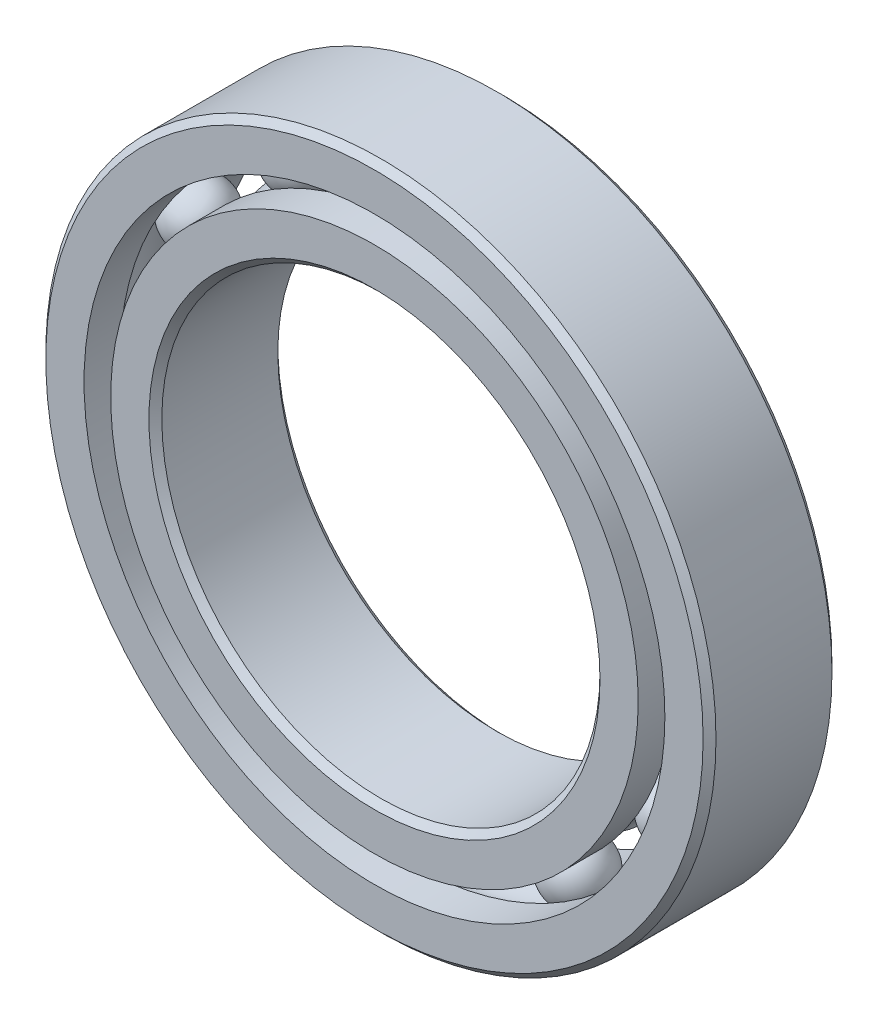
SolidWorks part; units mm, degrees
ref_plane "Front Plane" through (0, 0, 0) normal (0, 0, 1) x (1, 0, 0)
ref_plane "Top Plane" through (0, 0, 0) normal (0, 1, 0) x (1, 0, 0)
ref_plane "Right Plane" through (0, 0, 0) normal (1, 0, 0) x (0, 0, -1)
sketch "Sketch1" plane through (0, 0, 0) normal (1, 0, 0) x (0, 0, -1)
  line L0 (-2.5, 0) -> (2.5, 0) construction
  line L1 (0, 13) -> (0, -13) construction
  line L2 (2.25, 13) -> (-2.25, 13)
  line L3 (-2.25, 13) -> (-2.5, 12.75)
  line L4 (-2.5, 12.75) -> (-2.5, 11.2674)
  line L5 (-2.5, 11.2674) -> (-1.1111, 11.2674)
  line L6 (2.5, 11.2674) -> (1.1111, 11.2674)
  line L7 (2.5, 12.75) -> (2.5, 11.2674)
  line L8 (2.25, 13) -> (2.5, 12.75)
  line L9 (0, 13) -> (0, 10.75) construction
  line L10 (0, 10.75) -> (0, 8.5) construction
  arc A0 (-1.1111, 11.2674) -> (1.1111, 11.2674) centre (0, 10.75) cw
  point P14 (0, 8.5)
  point P15 (1.1111, 11.2674)
  dimension "Width" = 5
  dimension "OD" = 26
  dimension "D1" = 45
  dimension "D2" = 0.25
  dimension "Shaft Dia" = 17
  dimension "D3" = 2.2222
revolve "Revolve1" add sketch "Sketch1" angle 360 about L0
sketch "Sketch3" plane through (0, 0, 0) normal (1, 0, 0) x (0, 0, -1)
  line L0 (-2.5, 10.2326) -> (-1.1111, 10.2326)
  line L1 (0, 13) -> (0, -13) construction
  line L2 (-2.5, 12.75) -> (-2.5, 11.2674) construction
  line L3 (-2.5, 10.2326) -> (-2.5, 8.75)
  line L4 (-2.25, 13) -> (-2.5, 12.75) construction
  line L5 (-2.5, 8.75) -> (-2.25, 8.5)
  line L6 (-2.25, 8.5) -> (2.25, 8.5)
  line L7 (2.25, 13) -> (2.25, -13) construction
  line L8 (2.25, 8.5) -> (2.5, 8.75)
  line L9 (2.5, -12.75) -> (2.5, 12.75) construction
  line L10 (2.5, 8.75) -> (2.5, 10.2326)
  line L11 (2.5, 10.2326) -> (1.1111, 10.2326)
  line L13 (2.25, 13) -> (2.5, 12.75) construction
  arc A0 (1.1111, 11.2674) -> (-1.1111, 11.2674) centre (0, 10.75) ccw construction
  arc A1 (1.1111, 10.2326) -> (-1.1111, 10.2326) centre (0, 10.75) cw
revolve "Revolve3" add sketch "Sketch3" angle 360 about L0
sketch "Sketch4" plane through (0, 0, 0) normal (1, 0, 0) x (0, 0, -1)
  line L0 (-1.2257, 10.75) -> (1.2257, 10.75)
  arc A2 (-1.2257, 10.75) -> (1.2257, 10.75) centre (0, 10.75) cw
  arc A3 (1.1111, 11.2674) -> (-1.1111, 11.2674) centre (0, 10.75) ccw construction
revolve "Revolve4" add sketch "Sketch4" angle 360 about L0
ref_axis "Axis1" through (0, 0, -2.5) along (0, 0, 1)
pattern_circular "CirPattern1" count 12 every 30 about axis through (0, 0, -2.5) along (0, 0, 1) of bodies 104
sketch "Sketch5" plane through (0, 0, 0) normal (1, 0, 0) x (0, 0, -1)
  line L0 (-2.5, 11.2674) -> (-1.1111, 11.2674) construction
  line L1 (-2.375, 11.2674) -> (-1.2257, 11.2674)
  line L2 (-2.375, 11.2674) -> (-2.375, 10.2326)
  line L3 (-2.375, 10.2326) -> (-1.2257, 10.2326)
  line L4 (-1.2257, 11.2674) -> (-1.2257, 10.2326)
  line L5 (-2.5, 10.2326) -> (-1.1111, 10.2326) construction
  line L6 (2.5, 11.2674) -> (1.1111, 11.2674) construction
  line L7 (2.375, 11.2674) -> (1.2257, 11.2674)
  line L8 (2.375, 11.2674) -> (2.375, 10.2326)
  line L9 (2.375, 10.2326) -> (1.2257, 10.2326)
  line L10 (1.2257, 11.2674) -> (1.2257, 10.2326)
  line L11 (2.5, 10.2326) -> (1.1111, 10.2326) construction
  line L12 (-2.25, 13) -> (-2.5, 12.75) construction
  point P18 (-2.375, 12.875)
equation "\"D2@Sketch1\" = \"Width@Sketch1\"*.05"
equation "\"D3@Sketch1\" = \"Width@Sketch1\"/2.25"
equation "\"D2@CirPattern1\" = 360/\"Balls@CirPattern1\""
